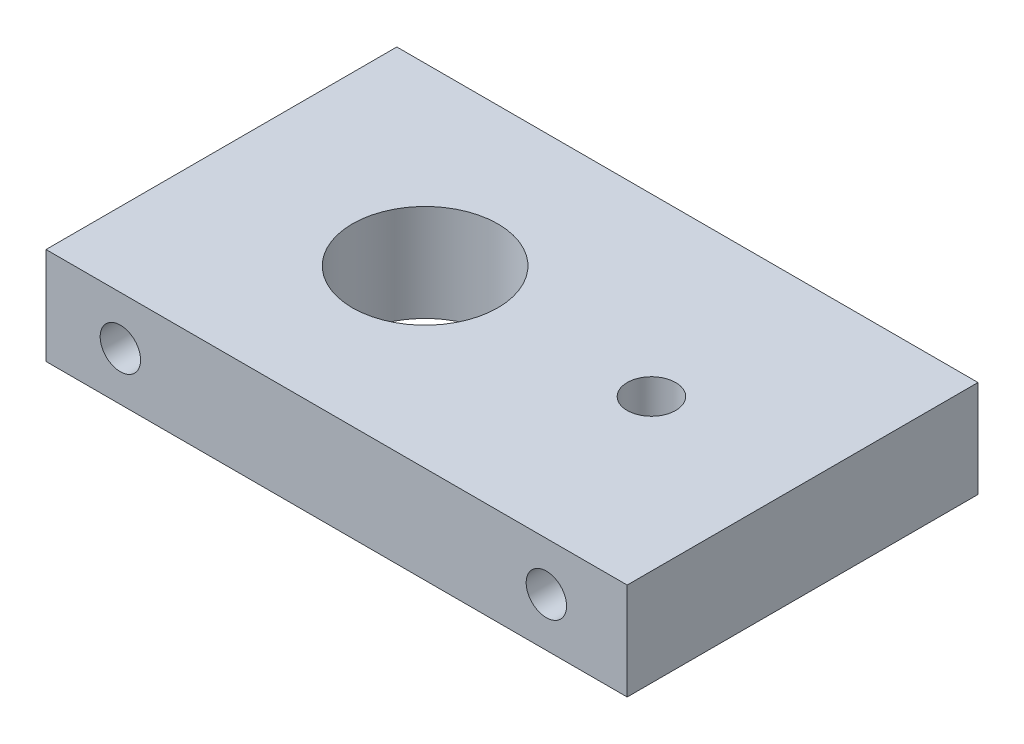
SolidWorks part; units mm, degrees
ref_plane "Ebene vorne" through (0, 0, 0) normal (0, 0, 1) x (1, 0, 0)
ref_plane "Ebene oben" through (0, 0, 0) normal (0, 1, 0) x (1, 0, 0)
ref_plane "Ebene rechts" through (0, 0, 0) normal (1, 0, 0) x (0, 0, -1)
sketch "Skizze1" plane through (0, 0, 0) normal (0, 0, 1) x (1, 0, 0)
  line L1 (-23.35, 231) -> (23.35, 231)
  line L2 (-23.35, 231) -> (-23.35, 237)
  line L3 (-23.35, 237) -> (23.35, 237)
  line L4 (23.35, 231) -> (23.35, 237)
  line L5 (-23.35, 231) -> (23.35, 237) construction
  line L6 (-23.35, 237) -> (23.35, 231) construction
  point P0 (0, 234)
sketch "Skizze2" plane through (0, 0, 0) normal (0, 1, 0) x (1, 0, 0)
  line L1 (-12.6, 12.65) -> (25.15, 12.65)
  line L2 (25.15, 12.65) -> (25.15, -12.65)
  line L3 (25.15, -12.65) -> (-12.6, -12.65)
  line L5 (-12.6, 10.85) -> (23.35, 10.85)
  line L6 (23.35, 10.85) -> (23.35, -10.85)
  line L7 (23.35, -10.85) -> (-12.6, -10.85)
  arc A0 (-12.6, 12.65) -> (-12.6, -12.65) centre (-12.6, 0) ccw
  arc A1 (-12.6, 10.85) -> (-12.6, -10.85) centre (-12.6, 0) ccw
sketch "Skizze3" plane through (0, 0, 0) normal (0, 0, 1) x (1, 0, 0)
  line L1 (-23.35, 231) -> (23.35, 231)
  line L2 (-23.35, 231) -> (-23.35, 237)
  line L3 (-23.35, 237) -> (23.35, 237)
  line L4 (23.35, 231) -> (23.35, 237)
  line L5 (-23.35, 231) -> (23.35, 237) construction
  line L6 (-23.35, 237) -> (23.35, 231) construction
  point P0 (0, 234)
extrude "Aufsatz-Linear austragen1" add sketch "Skizze3" along normal up to vertex (12.65 mm away) and the other way up to vertex (12.65 mm away) up to point (25.15, 0, 12.65) other way up to point (25.15, 0, -12.65)
sketch "Skizze4" plane through (0, 0, 0) normal (0, 1, 0) x (1, 0, 0)
  line L0 (23.35, -10.85) -> (23.35, 10.85)
  line L1 (23.35, 10.85) -> (23.35, -10.85) construction
  line L2 (23.35, 10.85) -> (-12.6, 10.85)
  line L3 (-76.8863, 0) -> (76.8863, 0) construction
  line L4 (23.35, -10.85) -> (-12.6, -10.85)
  line L5 (-12.6, 10.85) -> (-12.6, -10.85)
  point P15 (23.35, 0)
extrude "Schnitt-Linear austragen1" cut sketch "Skizze4" along normal up to surface (237 mm away) flip side to cut up to face at (0, 237, 0)
sketch "HoleLeadscrewLinearGuide" plane through (0, 0, 0) normal (0, 1, 0) x (1, 0, 0)
  circle A0 centre (14, 0) radius 1.5
  circle A1 centre (0, 0) radius 4.5
sketch "Skizze7" plane through (0, 0, 0) normal (0, 1, 0) x (1, 0, 0)
  circle A0 centre (0, 0) radius 4.5
  circle A1 centre (14, 0) radius 1.5
extrude "Schnitt-Linear austragen2" cut sketch "Skizze7" along normal up to surface (237 mm away) up to face at (5.375, 237, 0)
sketch "ThreadHolesSide" plane through (0, 0, 0) normal (0, 0, 1) x (1, 0, 0)
  line L0 (0, 234) -> (28.7572, 234) construction
  line L3 (0, 615) -> (28.7572, 615) construction
  circle A0 centre (18.35, 234) radius 1.25
  circle A1 centre (-8, 234) radius 1.25
  circle A2 centre (18.35, 615) radius 1.25
  circle A3 centre (-8, 615) radius 1.25
extrude "Schnitt-Linear austragen3" cut sketch "ThreadHolesSide" along normal blind 6 from surface starting at face at (5.375, 234, -10.85)
extrude "Schnitt-Linear austragen4" cut sketch "ThreadHolesSide<2>" against normal blind 6 from surface starting at face at (5.375, 234, 10.85)
sketch "ThreadHolesSide<2>" plane through (0, 0, 0) normal (0, 0, 1) x (1, 0, 0) same geometry as "ThreadHolesSide"
ref_axis "Achse1" through (18.35, 234, 4.85) along (0, 0, 1)
